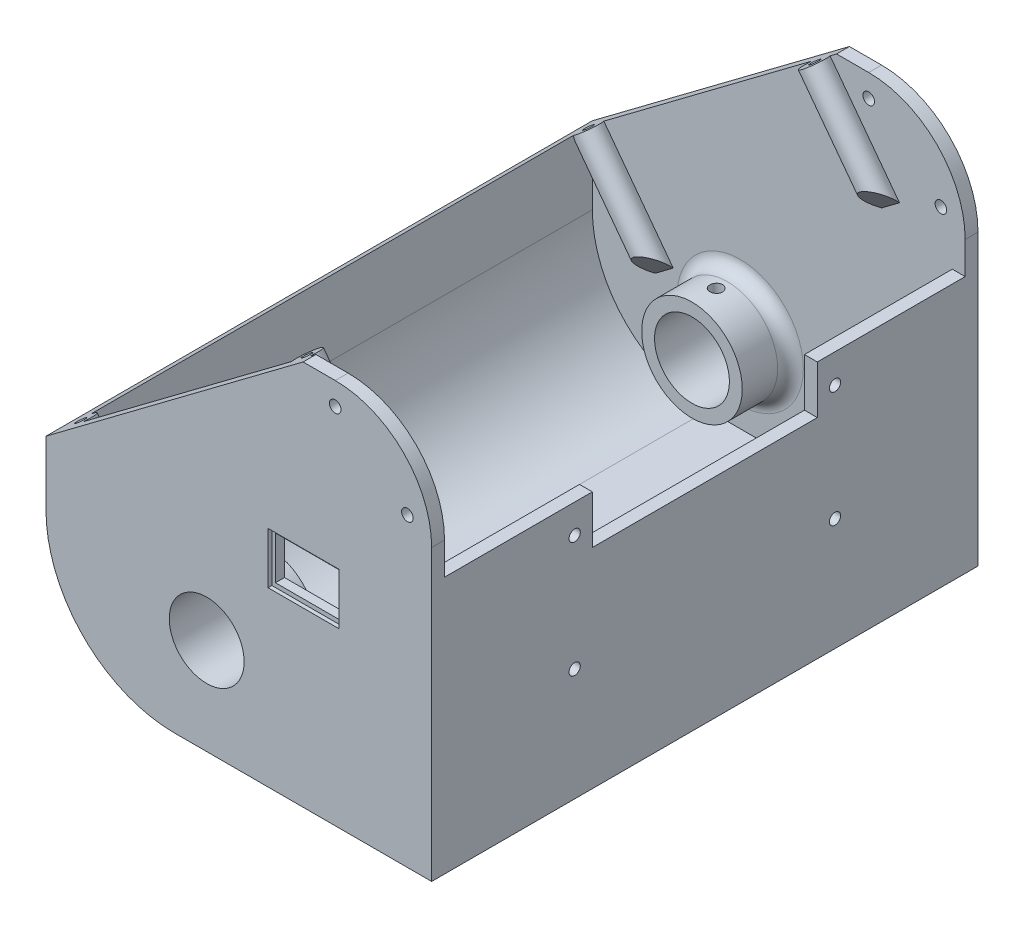
SolidWorks part; units mm, degrees
ref_plane "前视基准面" through (0, 0, 0) normal (0, 0, 1) x (1, 0, 0)
ref_plane "上视基准面" through (0, 0, 0) normal (0, 1, 0) x (1, 0, 0)
ref_plane "右视基准面" through (0, 0, 0) normal (1, 0, 0) x (0, 0, -1)
sketch "草图1" plane through (0, 0, 0) normal (0, 0, 1) x (1, 0, 0)
  line L0 (-6.571, -19.1611) -> (73.429, -19.1611)
  line L1 (73.429, -19.1611) -> (73.429, 70.8389)
  line L2 (43.429, 100.8389) -> (33.429, 100.8389)
  line L3 (33.429, 100.8389) -> (-46.571, 40.8389)
  line L4 (-46.571, 40.8389) -> (-46.571, 20.8389)
  line L5 (43.429, 96.8389) -> (16.4445, 96.8389) construction
  circle A0 centre (3.429, 10.8389) radius 11.65
  arc A1 (-6.571, -19.1611) -> (-46.571, 20.8389) centre (-6.571, 20.8389) cw
  arc A2 (73.429, 70.8389) -> (43.429, 100.8389) centre (43.429, 70.8389) ccw
  circle A3 centre (43.429, 70.8389) radius 26 construction
  circle A4 centre (43.429, 93.8389) radius 3 construction
  circle A5 centre (43.429, 93.8389) radius 1.8
  circle A6 centre (65.8789, 75.8389) radius 3 construction
  circle A7 centre (65.8789, 75.8389) radius 1.8
  point P9 (-46.571, -19.1611)
  point P13 (73.429, 100.8389)
  dimension "D1" = 30
  dimension "D6" = 70
  dimension "D7" = 23.3
  dimension "D8" = 40
  dimension "D9" = 30
  dimension "D10" = 52
  dimension "D11" = 6
  dimension "D12" = 3.6
  dimension "D13" = 6
  dimension "D14" = 3.6
  dimension "D15" = 5
  dimension "D2" = 120
  dimension "D3" = 120
  dimension "D4" = 100
  dimension "D5" = 60
extrude "凸台-拉伸1" add sketch "草图1" along normal blind 170
shell "抽壳2" thickness 4 removed face at (-6.571, 70.8389, 85)
sketch "草图10" plane through (73.429, 0, 0) normal (1, 0, 0) x (0, 0, -1)
  line L0 (-170, 100.8389) -> (-170, 70.8389) construction
  line L1 (-166, 129.8141) -> (-4, 129.8141)
  line L2 (-166, 129.8141) -> (-166, 60.8389)
  line L3 (-166, 60.8389) -> (-4, 60.8389)
  line L4 (-4, 129.8141) -> (-4, 60.8389)
  line L5 (0, 70.8389) -> (0, 100.8389) construction
  line L7 (-170, 70.8389) -> (0, 70.8389) construction
  dimension "D1" = 4
  dimension "D2" = 68.9753
  dimension "D3" = 4
  dimension "D4" = 10
extrude "切除-拉伸8" cut sketch "草图10" against normal blind 65
sketch "草图2" plane through (-36.3682, 48.491, 0) normal (-0.6, 0.8, 0) x (0.8, 0.6, 0)
  line L2 (-123.578, -85) -> (204.8739, -85) construction
  line L3 (87.2465, 0) -> (-12.7535, 0) construction
  line L4 (87.2465, -170) -> (-12.7535, -170) construction
  line L5 (37.2465, 28.1893) -> (37.2465, -212.24) construction
  line L7 (-12.7535, -170) -> (-12.7535, 0) construction
  line L8 (87.2465, -170) -> (87.2465, -166) construction
  circle A0 centre (81.2465, -6) radius 4
  circle A3 centre (-6.7535, -6) radius 4
  circle A5 centre (81.2465, -164) radius 4
  circle A7 centre (-6.7535, -164) radius 4
  dimension "D1" = 6
  dimension "D3" = 8
  dimension "D2" = 6
extrude "凸台-拉伸2" add sketch "草图2" against normal blind 30
ref_plane "基准面1" through (0, -12.1611, 0) normal (0, 1, 0) x (1, 0, 0)
sketch "草图3" plane through (0, -12.1611, 0) normal (0, 1, 0) x (1, 0, 0)
  line L0 (-61.5883, -85) -> (111.3368, -85) construction
  line L1 (-12.5614, -19) -> (36.2034, -19)
  line L2 (-12.5614, -19) -> (-12.5614, -151)
  line L3 (-12.5614, -151) -> (36.2034, -151)
  line L4 (36.2034, -19) -> (36.2034, -151)
  line L5 (-6.571, -4) -> (69.429, -4) construction
  line L6 (25.8577, -166) -> (-38.9997, -166) construction
  line L7 (25.8577, -4) -> (-38.9997, -4) construction
  dimension "D1" = 15
extrude "切除-拉伸1" cut sketch "草图3" along normal blind 57
sketch "草图4" plane through (-36.3682, 48.491, 0) normal (-0.6, 0.8, 0) x (0.8, 0.6, 0)
  line L0 (-55.4874, -85) -> (131.5309, -85) construction
  line L1 (77.7824, -4) -> (-3.2894, -4) construction
  line L2 (77.7824, -166) -> (-3.2894, -166) construction
  line L3 (37.2465, 31.2462) -> (37.2465, -199.084) construction
  line L4 (-12.7535, -170) -> (-12.7535, 0) construction
  line L5 (87.2465, -170) -> (87.2465, -166) construction
  circle A0 centre (-6.7535, -6) radius 1.5
  circle A1 centre (81.2465, -6) radius 1.5
  circle A2 centre (81.2465, -164) radius 1.5
  circle A3 centre (-6.7535, -164) radius 1.5
  dimension "D1" = 3
extrude "切除-拉伸2" cut sketch "草图4" against normal blind 20
sketch "草图5" plane through (0, -15.1611, 0) normal (0, 1, 0) x (1, 0, 0)
  line L0 (-83.0245, -85) -> (98.9543, -85) construction
  line L1 (33.429, 0) -> (-46.571, 0) construction
  line L2 (33.429, -170) -> (-46.571, -170) construction
  line L3 (73.429, -170) -> (73.429, 0) construction
  line L4 (23.429, -45) -> (39.429, -45) construction
  circle A0 centre (23.429, -45) radius 3.25
  circle A1 centre (39.429, -45) radius 3.25
  circle A2 centre (23.429, -125) radius 3.25
  circle A3 centre (39.429, -125) radius 3.25
  dimension "D1" = 16
  dimension "D2" = 6.5
  dimension "D3" = 34
  dimension "D4" = 40
extrude "切除-拉伸3" cut sketch "草图5" against normal blind 20
sketch "草图6" plane through (0, 100.8389, 0) normal (0, 1, 0) x (1, 0, 0)
  line L0 (3.429, 24.559) -> (3.429, -186.1005) construction
  line L1 (-12.221, -151) -> (-12.221, -166) construction
  line L2 (19.079, -166) -> (19.079, -151) construction
  line L3 (25.8577, -4) -> (-38.9997, -4) construction
  line L4 (25.8577, -166) -> (-38.9997, -166) construction
  circle A0 centre (3.429, -158.5) radius 1.95
  circle A1 centre (3.429, -11.5) radius 1.95
  dimension "D1" = 3.9
  dimension "D2" = 3.9
  dimension "D3" = 7.5
  dimension "D4" = 7.5
extrude "切除-拉伸4" cut sketch "草图6" against normal blind 93
fillet "圆角1" radius 4 2 edges at (19.079, 10.8389, 166) (19.079, 10.8389, 4)
fillet "圆角2" radius 6 4 edges at (-23.771, 20.4389, 4) (46.629, 73.2389, 4) (46.629, 73.2389, 166) (-23.771, 20.4389, 166) profile chamfer
sketch "草图7" plane through (73.429, 0, 0) normal (1, 0, 0) x (0, 0, -1)
  line L0 (-85, 120.2356) -> (-85, -47.1901) construction
  line L1 (-170, -19.1611) -> (-170, 70.8389) construction
  line L2 (0, -19.1611) -> (0, 70.8389) construction
  line L3 (-166, 60.8389) -> (-4, 60.8389) construction
  line L4 (-120, 60.8389) -> (-50, 60.8389)
  line L5 (-120, 60.8389) -> (-120, 45.8389)
  line L6 (-120, 45.8389) -> (-50, 45.8389)
  line L7 (-50, 60.8389) -> (-50, 45.8389)
  dimension "D1" = 15
  dimension "D2" = 70
extrude "切除-拉伸5" cut sketch "草图7" against normal blind 39
sketch "草图8" plane through (0, 0, 170) normal (0, 0, 1) x (1, 0, 0)
  line L2 (73.429, -19.1611) -> (73.429, 70.8389) construction
  line L3 (23.629, 49.2389) -> (43.429, 49.2389)
  line L4 (23.629, 49.2389) -> (23.629, 35.8389)
  line L5 (23.629, 35.8389) -> (43.429, 35.8389)
  line L6 (43.429, 49.2389) -> (43.429, 35.8389)
  circle A1 centre (3.429, 10.8389) radius 11.65 construction
  dimension "D1" = 19.8
  dimension "D2" = 13.4
  dimension "D3" = 30
  dimension "D4" = 25
sketch "草图9" plane through (0, -19.1611, 0) normal (0, -1, 0) x (1, 0, 0)
  line L0 (-6.571, 170) -> (73.429, 170) construction
  line L1 (44.429, 166) -> (69.429, 166)
  line L2 (44.429, 166) -> (44.429, 141)
  line L3 (44.429, 141) -> (69.429, 141)
  line L4 (69.429, 166) -> (69.429, 141)
  line L5 (73.429, 170) -> (73.429, 0) construction
  dimension "D1" = 4
  dimension "D2" = 25
  dimension "D3" = 4
extrude "切除-拉伸7" cut sketch "草图9" against normal blind 39
sketch "草图11" plane through (69.429, 0, 0) normal (-1, 0, 0) x (0, 0, 1)
  line L0 (85, 102.6125) -> (85, -30.4808) construction
  line L1 (0, 100.8389) -> (0, 40.8389) construction
  line L2 (170, 100.8389) -> (170, 40.8389) construction
  line L3 (170, -19.1611) -> (0, -19.1611) construction
  circle A0 centre (44.5, 51.8389) radius 1.75
  circle A1 centre (44.5, 15.8389) radius 1.75
  circle A2 centre (125.5, 15.8389) radius 1.75
  circle A3 centre (125.5, 51.8389) radius 1.75
  dimension "D1" = 3.5
  dimension "D2" = 36
  dimension "D3" = 35
  dimension "D4" = 81
extrude "切除-拉伸9" cut sketch "草图11" against normal blind 10
extrude "切除-拉伸10" cut sketch "草图8" against normal blind 10
sketch "草图12" plane through (0, 0, 170) normal (0, 0, 1) x (1, 0, 0)
  line L0 (8.6296, 42.5389) -> (68.7821, 42.5389) construction
  line L1 (22.529, 50.5389) -> (44.529, 50.5389)
  line L2 (22.529, 50.5389) -> (22.529, 34.5389)
  line L3 (22.529, 34.5389) -> (44.529, 34.5389)
  line L4 (44.529, 50.5389) -> (44.529, 34.5389)
  line L5 (43.429, 49.2389) -> (23.629, 49.2389) construction
  line L6 (23.629, 35.8389) -> (43.429, 35.8389) construction
  line L7 (33.529, 64.1685) -> (33.529, 24.3722) construction
  line L8 (23.629, 49.2389) -> (23.629, 35.8389) construction
  line L9 (43.429, 35.8389) -> (43.429, 49.2389) construction
  dimension "D1" = 22
  dimension "D2" = 16
extrude "切除-拉伸11" cut sketch "草图12" against normal blind 1.2
